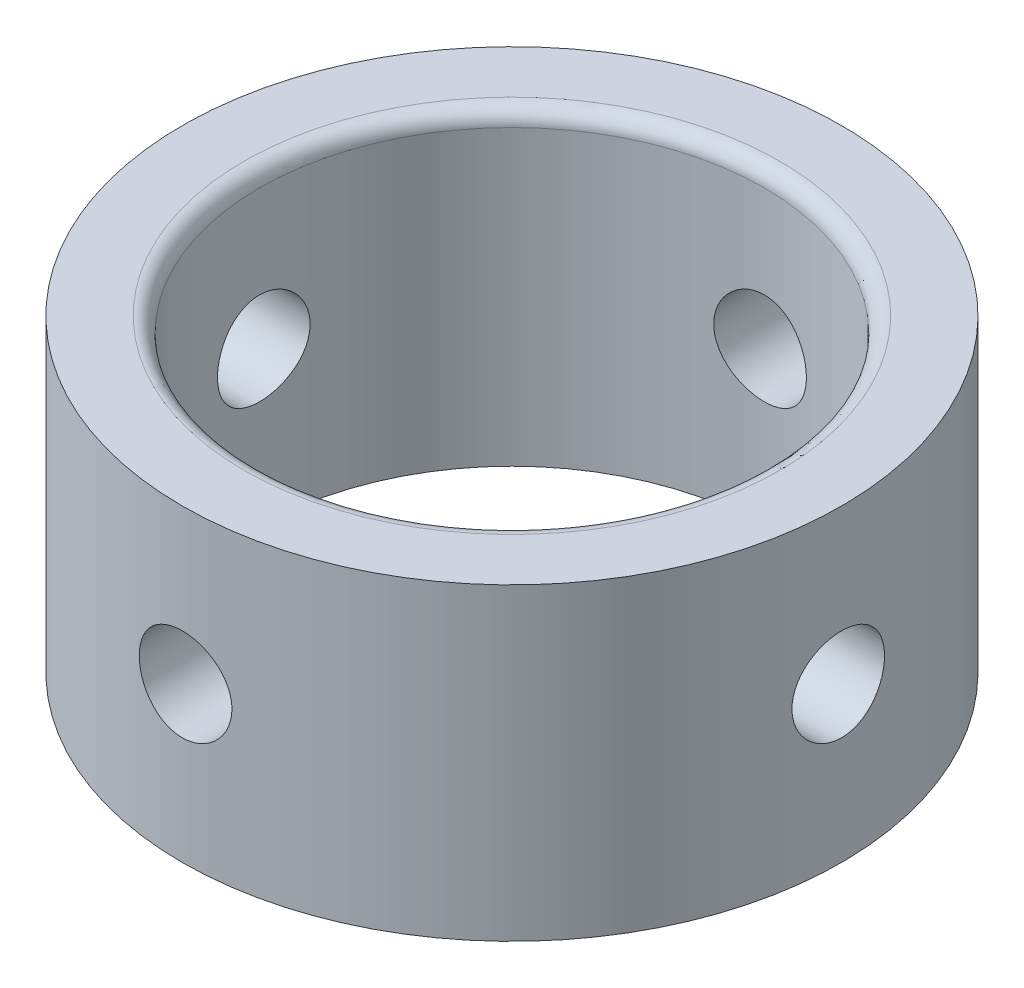
SolidWorks part; units mm, degrees
ref_plane "Front Plane" through (0, 0, 0) normal (0, 0, 1) x (1, 0, 0)
ref_plane "Top Plane" through (0, 0, 0) normal (0, 1, 0) x (1, 0, 0)
ref_plane "Right Plane" through (0, 0, 0) normal (1, 0, 0) x (0, 0, -1)
sketch "Sketch1" plane through (0, 0, 0) normal (0, 1, 0) x (1, 0, 0)
  circle A0 centre (0, 0) radius 16.35
  circle A1 centre (0, 0) radius 21.35
  dimension "D1" = 32.7
  dimension "D2" = 5
extrude "Boss-Extrude1" add sketch "Sketch1" along normal blind 20
fillet "Fillet1" radius 1 1 edges at (0, 20, 16.35)
ref_plane "Plane1" through (21.35, 0, 0) normal (1, 0, 0) x (0, 0, -1)
sketch "Sketch2" plane through (21.35, 0, 0) normal (1, 0, 0) x (0, 0, -1)
  line L0 (0, 20) -> (0, 0) construction
  line L1 (21.35, 20) -> (-21.35, 20) construction
  circle A0 centre (0, 10) radius 3
  dimension "D1" = 6
extrude "Cut-Extrude1" cut sketch "Sketch2" against normal blind 10
ref_axis "Axis1" through (0, 19, 0) along (0, -1, 0)
pattern_circular "CirPattern1" count 4 over 360 about axis through (0, 19, 0) along (0, -1, 0) of "Cut-Extrude1"
